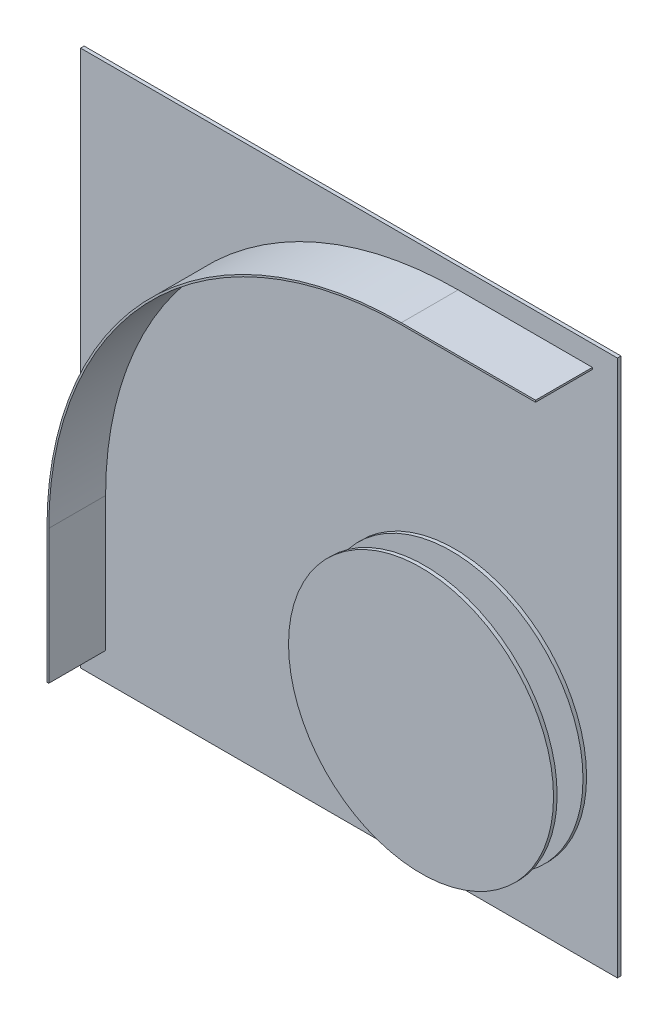
SolidWorks part; units mm, degrees
note: The reader was unsure of these and kept them because the rebuilt part matched: shared geometry of "Sketch1<4>".
ref_plane "Front Plane" through (0, 0, 0) normal (0, 0, 1) x (1, 0, 0)
ref_plane "Top Plane" through (0, 0, 0) normal (0, 1, 0) x (1, 0, 0)
ref_plane "Right Plane" through (0, 0, 0) normal (1, 0, 0) x (0, 0, -1)
sketch "Sketch1" plane through (0, 0, 0) normal (0, 0, 1) x (1, 0, 0)
  line L0 (0, 394) -> (0, 0) construction
  line L1 (0, 0) -> (-394, 0) construction
  line L2 (-394, 0) -> (-394, -150)
  line L3 (0, 394) -> (150, 394)
  circle A0 centre (0, 0) radius 147
  arc A1 (-394, 0) -> (0, 394) centre (0, 0) cw
  circle A2 centre (0, 0) radius 153
  dimension "D1" = 294
  dimension "D2" = 247
  dimension "D4" = 6
  dimension "D3" = 150
extrude "Boss-Extrude1" add sketch "Sketch1" along normal blind 4 contours A0
extrude "Extrude-Thin1" add sketch "Sketch1<4>" along normal blind 60 and the other way blind 5.5 separate body thin contours L2 A1 L3
sketch "Sketch1<4>" plane through (0, 0, 0) normal (0, 0, 1) x (1, 0, 0) same geometry as "Sketch1"
ref_plane "Plane1" through (0, 0, 34) normal (0, 0, 1) x (1, 0, 0)
sketch "Sketch2" plane through (0, 0, 34) normal (0, 0, 1) x (1, 0, 0)
  circle A0 centre (0, 0) radius 148.071
extrude "Boss-Extrude2" add sketch "Sketch2" along normal blind 4 separate body
sketch "Sketch3" plane through (0, 0, 4) normal (0, 0, 1) x (1, 0, 0)
  circle A0 centre (0, 84.5463) radius 15
  circle A1 centre (84.5463, 0) radius 15
  circle A2 centre (0, -84.5463) radius 15
  circle A3 centre (-84.5463, 0) radius 15
  point P11 (0, 0)
  dimension "D1" = 30
extrude "Boss-Extrude3" add sketch "Sketch3" along normal blind 30
ref_plane "Plane2" through (0, 0, -3.5) normal (0, 0, 1) x (1, 0, 0)
sketch "Sketch5" plane through (0, 0, -3.5) normal (0, 0, 1) x (1, 0, 0)
  line L1 (-422.012, 419.0338) -> (177.988, 419.0338)
  line L2 (-422.012, 419.0338) -> (-422.012, -180.9662)
  line L3 (-422.012, -180.9662) -> (177.988, -180.9662)
  line L4 (177.988, 419.0338) -> (177.988, -180.9662)
  dimension "D1" = 600
extrude "Boss-Extrude5" add sketch "Sketch5" against normal blind 4 separate body
